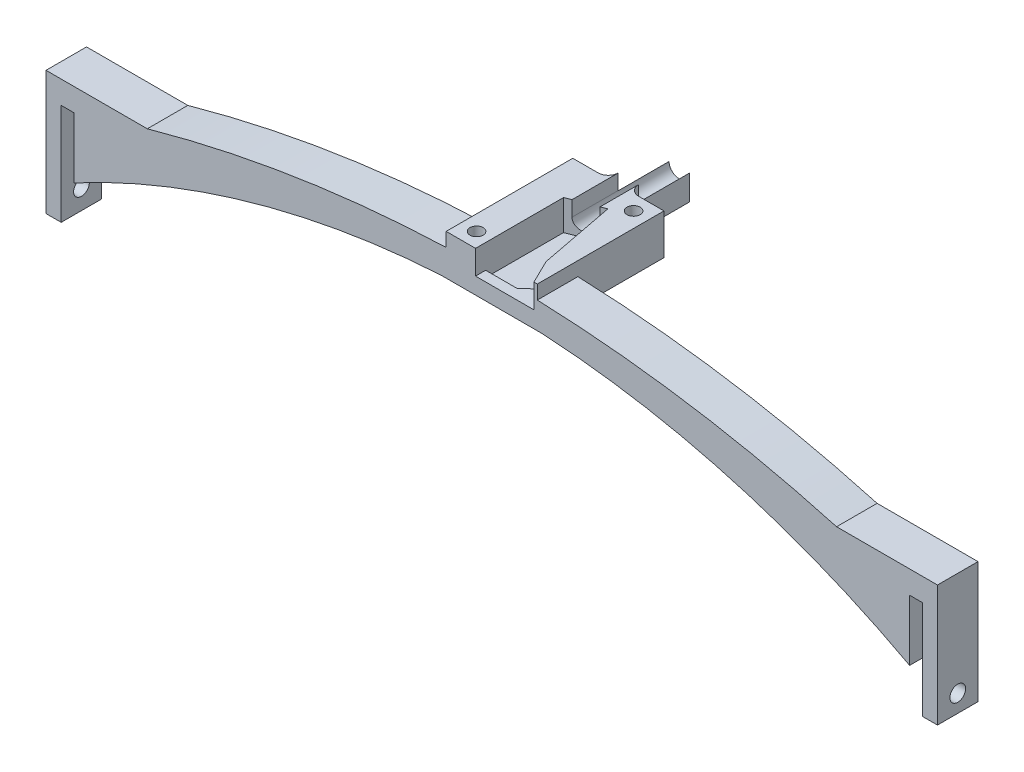
SolidWorks part; units mm, degrees
material "ABS"
ref_plane "Front Plane" through (0, 0, 0) normal (0, 0, 1) x (1, 0, 0)
ref_plane "Top Plane" through (0, 0, 0) normal (0, 1, 0) x (1, 0, 0)
ref_plane "Right Plane" through (0, 0, 0) normal (1, 0, 0) x (0, 0, -1)
sketch "Sketch1" plane through (0, 0, 0) normal (0, 0, 1) x (1, 0, 0)
  line L1 (0, 0) -> (2.5, 0) construction
  line L2 (0, 0) -> (0, 12) construction
  line L3 (0, 12) -> (2.5, 12) construction
  line L4 (2.5, 0) -> (2.5, 12) construction
  line L5 (167.5, 12) -> (170, 12) construction
  line L6 (167.5, 12) -> (167.5, 0) construction
  line L7 (167.5, 0) -> (170, 0) construction
  line L8 (170, 12) -> (170, 0) construction
  line L9 (-3, 0) -> (-3, 16.5)
  line L10 (-3, 16.5) -> (17, 16.5)
  line L11 (0, 0) -> (0, 12)
  line L12 (0, 12) -> (2.5, 12)
  line L13 (2.5, 12) -> (2.5, 0)
  line L14 (167.5, 12) -> (167.5, 0)
  line L15 (167.5, 12) -> (170, 12)
  line L16 (170, 12) -> (170.006, 12.0368)
  line L17 (170, 0) -> (170.006, 12.0368)
  line L19 (173, 0.5442) -> (173, 16.5)
  line L20 (173, 16.5) -> (153.0793, 16.5)
  line L21 (170, 0) -> (170, -7.4558)
  line L22 (170, -7.4558) -> (173, -7.4558)
  line L23 (173, -7.4558) -> (173, 0.5442)
  line L24 (-3, 16.5) -> (173, 16.5) construction
  line L25 (85, 16.5) -> (85, -29.5245) construction
  line L29 (-3, 0) -> (-3, -8)
  line L30 (-3, -8) -> (0, -8)
  line L31 (0, -8) -> (0, 0)
  line L32 (75, 20.4599) -> (95, 20.4599)
  arc A0 (2.5, 0) -> (75, 20.4599) centre (85, -153.6577) cw
  arc A1 (17, 16.5) -> (153.0793, 16.5) centre (85.0397, -225.6527) cw
  arc A2 (95, 20.4599) -> (167.5, 0) centre (85, -153.6577) cw
  dimension "D6" = 3
  dimension "D1" = 2.5
  dimension "D2" = 2.5
  dimension "D3" = 165
  dimension "D4" = 12
  dimension "D5" = 12
  dimension "D7" = 20
  dimension "D8" = 8
  dimension "D9" = 8
  dimension "D10" = 3
  dimension "D11" = 20
  dimension "D12" = 10
  dimension "D13" = 3
  dimension "D14" = 4.5
extrude "Boss-Extrude1" add sketch "Sketch1" along normal blind 8
sketch "Sketch2" plane through (-3, 0, 0) normal (-1, 0, 0) x (0, 0, 1)
  line L1 (0, 16.5) -> (0, -8) construction
  line L2 (8, 16.5) -> (0, 16.5) construction
  circle A0 centre (4, -4) radius 1.55
  point P8 (-5.9664, 3.0519)
  dimension "D1" = 3.1
  dimension "D2" = 20.5
  dimension "D3" = 4
extrude "Cut-Extrude1" cut sketch "Sketch2" against normal through all contours A0
sketch "Sketch3" plane through (0, 0, 0) normal (0, 1, 0) x (1, 0, 0)
  line L5 (94, 17) -> (87, 17)
  line L6 (94, 17) -> (94, -8)
  line L7 (94, -8) -> (76, -8)
  line L8 (76, 17) -> (76, -8)
  line L9 (173, -8) -> (173, 0) construction
  line L12 (83, 17) -> (76, 17)
  line L14 (83, 17) -> (83, 29)
  line L15 (83, 29) -> (87, 29)
  line L16 (87, 17) -> (87, 29)
  circle A0 centre (91, 14) radius 1.3
  circle A1 centre (79, -5) radius 1.3
  dimension "D4" = 2.6
  dimension "D7" = 2.6
  dimension "D1" = 18
  dimension "D2" = 25
  dimension "D3" = 79
  dimension "D5" = 4
  dimension "D6" = 7
  dimension "D8" = 3
  dimension "D9" = 3
  dimension "D10" = 3
  dimension "D11" = 3
  dimension "D12" = 12
extrude "Boss-Extrude3" add sketch "Sketch3" along normal blind 8 from surface starting at face at (85, 20.4599, 4)
sketch "Sketch5" plane through (0, 0, 8) normal (0, 0, 1) x (1, 0, 0)
  line L0 (95, 20.4599) -> (75, 20.4599) construction
  line L3 (82.9995, 25.4599) -> (82.9995, 28.4599)
  line L4 (94, 28.4599) -> (76, 28.4599) construction
  line L5 (82.9995, 28.4599) -> (87.0005, 28.4599)
  line L6 (87.0005, 28.4599) -> (87.0005, 25.4599)
  line L7 (-3, 16.5) -> (173, 16.5) construction
  line L8 (85, 16.5) -> (85, 43.7245) construction
  arc A0 (82.9995, 25.4599) -> (87.0005, 25.4599) centre (85, 25.4599) ccw
  dimension "D1" = 4.001
  dimension "D2" = 5
extrude "Cut-Extrude2" cut sketch "Sketch5" against normal blind 40 from offset 2 offset against normal yes
extrude "Cut-Extrude3" cut sketch "Sketch3<3>" against normal through all both and the other way through all contours A1 region at (79, 0, 5)
sketch "Sketch3<3>" plane through (0, 0, 0) normal (0, 1, 0) x (1, 0, 0) same geometry as "Sketch3"
sketch "Sketch6" plane through (0, 28.4599, 0) normal (0, 1, 0) x (1, 0, 0)
  line L0 (81.7995, 9.38) -> (88.1135, 11.8088)
  line L1 (88.1135, 11.8088) -> (91.0245, -3.2881)
  line L2 (91.0245, -3.2881) -> (87.9495, -6)
  line L3 (87.9495, -6) -> (81.7995, -6)
  line L4 (81.7995, -6) -> (81.7995, 9.38)
  line L5 (87.0005, -6) -> (82.9995, -6) construction
  line L7 (82.9995, 17) -> (82.9995, -6) construction
  point P2 (0, 0)
  point P7 (80.545, 8.7586)
  point P8 (80.5689, 8.7586)
  dimension "D1" = 6.765
  dimension "D2" = 6.15
  dimension "D3" = 15.375
  dimension "D4" = 4.1
  dimension "D5" = 9.225
  dimension "D6" = 1.2
  dimension "D7" = 15.38
extrude "Cut-Extrude4" cut sketch "Sketch6" against normal blind 6
sketch "Sketch7" plane through (0, 28.4599, 0) normal (0, 1, 0) x (1, 0, 0)
  line L0 (91.0245, -3.2881) -> (93.3288, -8)
  line L1 (94, -8) -> (76, -8) construction
  line L2 (93.3288, -8) -> (81.7995, -8)
  line L3 (81.7995, -8) -> (81.7995, -6)
  line L4 (81.7995, -6) -> (87.9495, -6)
  line L5 (87.9495, -6) -> (91.0245, -3.2881)
  dimension "D1" = 90
  dimension "D2" = 2
  dimension "D3" = 11.5293
  dimension "D4" = 6.15
  dimension "D5" = 4.1
  dimension "D6" = 5.2452
  dimension "D7" = 74.651
extrude "Cut-Extrude5" cut sketch "Sketch7" against normal blind 4.75
fillet "Fillet1" radius 2 2 edges at (87, 22.9375, -17) (83, 22.9375, -17)
